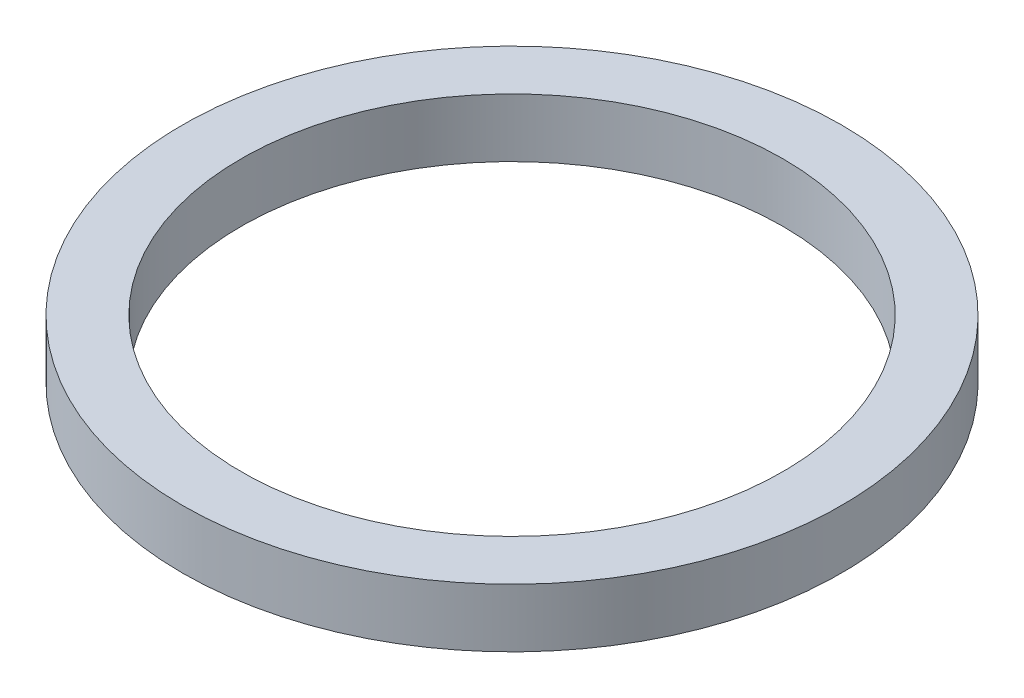
SolidWorks part; units mm, degrees
ref_plane "Front Plane" through (0, 0, 0) normal (0, 0, 1) x (1, 0, 0)
ref_plane "Top Plane" through (0, 0, 0) normal (0, 1, 0) x (1, 0, 0)
ref_plane "Right Plane" through (0, 0, 0) normal (1, 0, 0) x (0, 0, -1)
sketch "Sketch1" plane through (0, 0, 0) normal (0, 0, 1) x (1, 0, 0)
  line L0 (37, 8) -> (37, 0)
  line L1 (37, 0) -> (45, 0)
  line L2 (45, 0) -> (45, 8)
  line L3 (45, 8) -> (37, 8)
  line L4 (0, 0) -> (0, 37.6337) construction
  dimension "D1" = 8
  dimension "D2" = 8
  dimension "D3" = 45
revolve "Revolve1" add sketch "Sketch1" angle 360 about L4
ref_plane "TopPlane" through (0, 8, 0) normal (0, 1, 0) x (1, 0, 0)
ref_plane "BottomPlane" through (0, 0, 0) normal (0, -1, 0) x (-1, 0, 0)
ref_axis "CenterAxis" through (0, 8, 0) along (0, -1, 0)
